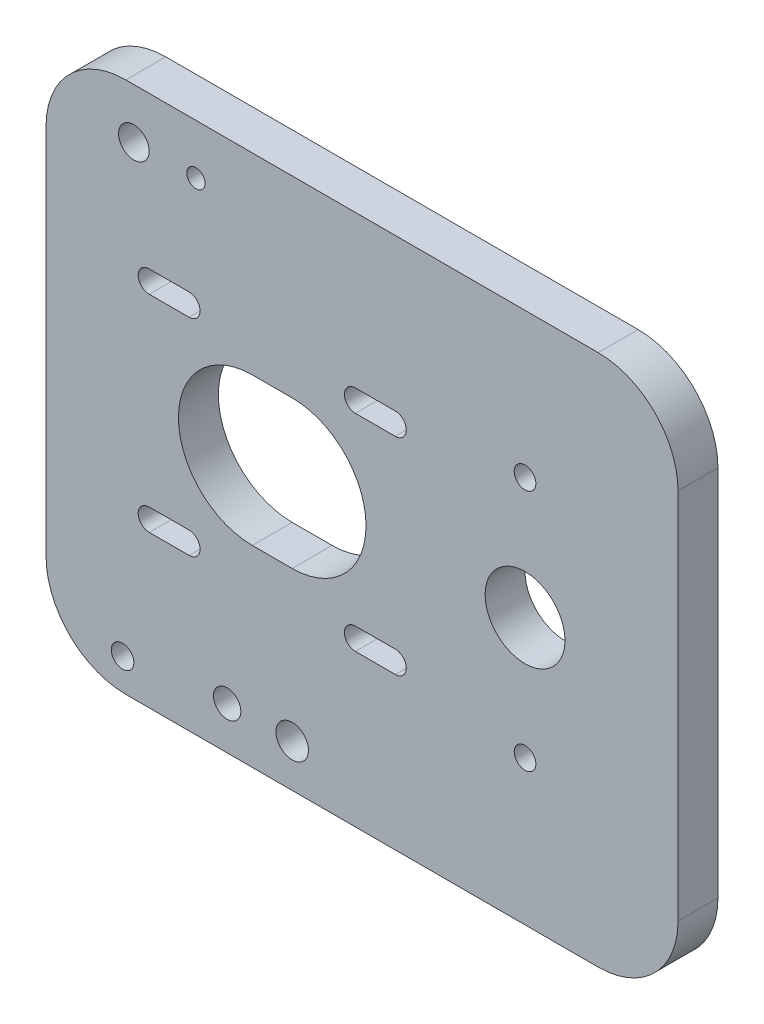
SolidWorks part; units mm, degrees
ref_plane "Alzado" through (0, 0, 0) normal (0, 0, 1) x (1, 0, 0)
ref_plane "Planta" through (0, 0, 0) normal (0, 1, 0) x (1, 0, 0)
ref_plane "Vista lateral" through (0, 0, 0) normal (1, 0, 0) x (0, 0, -1)
sketch "Croquis1" plane through (0, 0, 0) normal (0, 0, 1) x (1, 0, 0)
  line L1 (0, 0) -> (95, 0)
  line L2 (0, 0) -> (0, 80)
  line L3 (0, 80) -> (95, 80)
  line L4 (95, 0) -> (95, 80)
  dimension "D1" = 80
  dimension "D2" = 95
extrude "Saliente-Extruir1" add sketch "Croquis1" along normal blind 6
sketch "Croquis2" plane through (0, 0, 0) normal (0, 0, -1) x (-1, 0, 0)
  line L0 (0, 80) -> (0, 0) construction
  line L1 (0, 40) -> (-95, 40) construction
  line L4 (-95, 0) -> (-95, 80) construction
  line L7 (-31, 40) -> (-37, 40) construction
  line L10 (-31, 28.9) -> (-37, 28.9)
  line L19 (-31, 51.1) -> (-37, 51.1)
  line L20 (-15.5, 24.5) -> (-21.5, 24.5) construction
  line L21 (-15.5, 22.85) -> (-21.5, 22.85)
  line L22 (-15.5, 26.15) -> (-21.5, 26.15)
  line L23 (-46.5, 55.5) -> (-52.5, 55.5) construction
  line L24 (-46.5, 53.85) -> (-52.5, 53.85)
  line L25 (-46.5, 57.15) -> (-52.5, 57.15)
  line L26 (-46.5, 24.5) -> (-52.5, 24.5) construction
  line L27 (-46.5, 22.85) -> (-52.5, 22.85)
  line L28 (-46.5, 26.15) -> (-52.5, 26.15)
  line L29 (-15.5, 55.5) -> (-21.5, 55.5) construction
  line L30 (-15.5, 53.85) -> (-21.5, 53.85)
  line L31 (-15.5, 57.15) -> (-21.5, 57.15)
  line L32 (-72, 0) -> (-72, 80) construction
  line L33 (0, 0) -> (-95, 0) construction
  line L34 (-95, 80) -> (0, 80) construction
  line L35 (-63, 0) -> (-63, 80) construction
  circle A5 centre (-72, 40) radius 6
  circle A15 centre (-72, 21.75) radius 1.625
  circle A16 centre (-72, 58.25) radius 1.625
  arc A19 (-31, 28.9) -> (-31, 51.1) centre (-31, 40) ccw
  arc A20 (-37, 51.1) -> (-37, 28.9) centre (-37, 40) ccw
  arc A21 (-15.5, 22.85) -> (-15.5, 26.15) centre (-15.5, 24.5) ccw
  arc A22 (-21.5, 26.15) -> (-21.5, 22.85) centre (-21.5, 24.5) ccw
  arc A23 (-46.5, 53.85) -> (-46.5, 57.15) centre (-46.5, 55.5) ccw
  arc A24 (-52.5, 57.15) -> (-52.5, 53.85) centre (-52.5, 55.5) ccw
  arc A25 (-46.5, 22.85) -> (-46.5, 26.15) centre (-46.5, 24.5) ccw
  arc A26 (-52.5, 26.15) -> (-52.5, 22.85) centre (-52.5, 24.5) ccw
  arc A27 (-15.5, 53.85) -> (-15.5, 57.15) centre (-15.5, 55.5) ccw
  arc A28 (-21.5, 57.15) -> (-21.5, 53.85) centre (-21.5, 55.5) ccw
  circle A29 centre (-11.5055, 4.7316) radius 1.6929
  circle A30 centre (-27.2212, 6.4245) radius 2.0575
  circle A31 centre (-37, 6.4245) radius 2.4446
  circle A32 centre (-13.1984, 72.4694) radius 2.3016
  circle A33 centre (-22.5319, 72.4694) radius 1.3716
  point P6 (-34, 40)
  point P19 (-18.5, 24.5)
  point P28 (-49.5, 55.5)
  point P35 (-49.5, 24.5)
  point P48 (-18.5, 55.5)
  dimension "D2" = 6
  dimension "D3" = 11.1
  dimension "D4" = 3.3
  dimension "D5" = 6
  dimension "D6" = 12
  dimension "D13" = 3.25
  dimension "D14" = 3.25
  dimension "D7" = 15.5
  dimension "D8" = 15.5
  dimension "D9" = 3.3
  dimension "D10" = 6
  dimension "D11" = 23
  dimension "D12" = 40
  dimension "D15" = 18.25
  dimension "D16" = 18.25
  dimension "D17" = 3.3
  dimension "D18" = 6
  dimension "D19" = 3.3
  dimension "D20" = 6
  dimension "D21" = 15.5
  dimension "D22" = 15.5
  dimension "D23" = 15.5
  dimension "D24" = 15.5
  dimension "D25" = 15.5
  dimension "D26" = 15.5
  dimension "D27" = 38
  dimension "D28" = 26
extrude "Cortar-Extruir1" cut sketch "Croquis2" against normal through all
fillet "Redondeo1" radius 12 4 edges at (95, 0, 3) (95, 80, 3) (0, 0, 3) (0, 80, 3)
